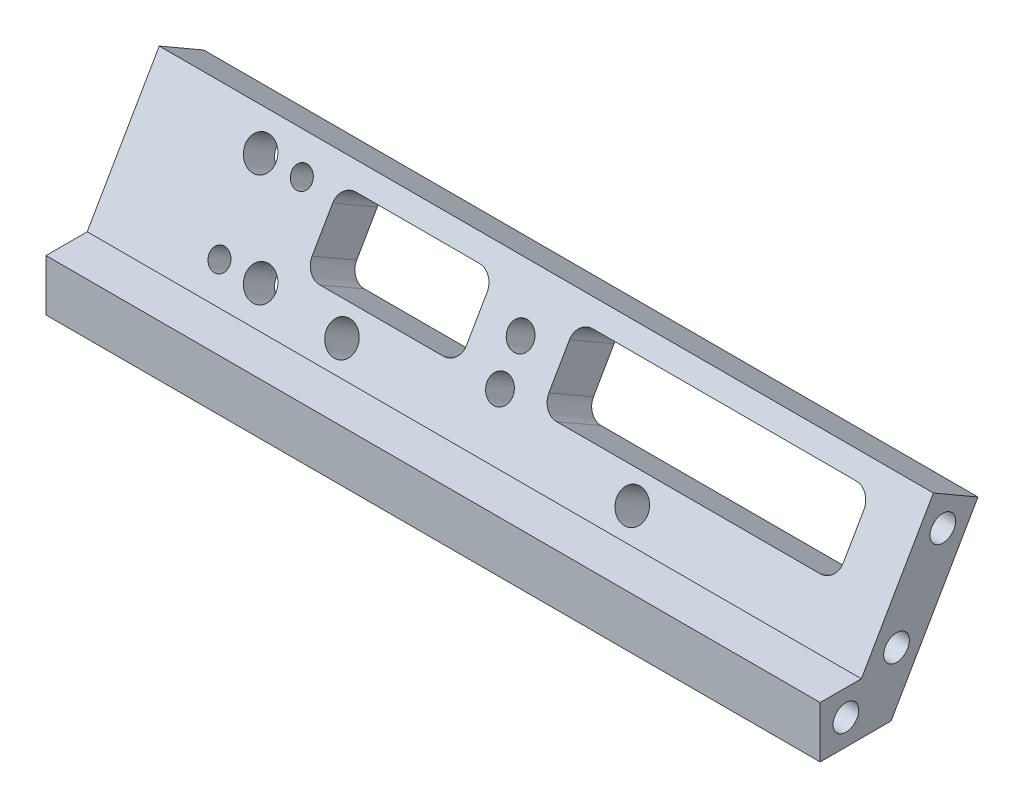
SolidWorks part; units mm, degrees
ref_plane "Front Plane" through (0, 0, 0) normal (0, 0, 1) x (1, 0, 0)
ref_plane "Top Plane" through (0, 0, 0) normal (0, 1, 0) x (1, 0, 0)
ref_plane "Right Plane" through (0, 0, 0) normal (1, 0, 0) x (0, 0, -1)
sketch "Sketch1" plane through (0, 0, 0) normal (1, 0, 0) x (0, 0, -1)
  line L0 (0, 0) -> (6.8868, 0)
  line L1 (6.8868, 0) -> (15.3301, 14.6244)
  line L2 (15.3301, 14.6244) -> (11, 17.1244)
  line L3 (11, 17.1244) -> (4, 5)
  line L4 (4, 5) -> (0, 5)
  line L5 (0, 5) -> (0, 0)
  dimension "D1" = 5
  dimension "D2" = 14
  dimension "D3" = 120
  dimension "D4" = 4
extrude "Boss-Extrude1" add sketch "Sketch1" along normal blind 75.2
hole_wizard "Tap Drill for M3x0.5 Tap1" positions "Sketch3" profile "Sketch2" hole size "M3x0.5" standard "ANSI Metric"
sketch "Sketch3" plane through (75.2, 0, 0) normal (1, 0, 0) x (0, 0, -1)
  line L0 (0, 5) -> (0, 0) construction
  line L1 (6.8868, 0) -> (15.3301, 14.6244) construction
  line L2 (15.3301, 14.6244) -> (11, 17.1244) construction
  line L3 (0, 0) -> (6.8868, 0) construction
  line L4 (11.9151, 13.7093) -> (7.4151, 5.9151) construction
  point P0 (2.5, 2.5)
  point P2 (7.4151, 5.9151)
  point P4 (11.9151, 13.7093)
  dimension "D1" = 2.5
  dimension "D2" = 2.5
  dimension "D3" = 2.5
  dimension "D4" = 9
  dimension "D5" = 2.5
sketch "Sketch2" plane through (75.2, 2.5, -2.5) normal (0, 1, 0) x (0, 0, -1)
  line L0 (0, 0) -> (0, 3.7511)
  line L1 (0, 3.7511) -> (1.25, 3)
  line L2 (1.25, 3) -> (1.25, 0)
  line L5 (1.25, 0) -> (0, 0)
  line L10 (0, 3.7511) -> (-1.25, 3) construction
  line L11 (0, -6.35) -> (0, 107.95) construction
  dimension "Hole Dia." = 2.5
  dimension "Hole Depth" = 3
  dimension "Drill Angle" = 118
hole_wizard "Tap Drill for M3x0.5 Tap2" positions "Sketch5" profile "Sketch4" hole size "M3x0.5" standard "ANSI Metric"
sketch "Sketch5" plane through (0, 0, 0) normal (-1, 0, 0) x (0, 0, 1)
  line L0 (-11.9151, 13.7093) -> (-7.4151, 5.9151) construction
  line L2 (-11, 17.1244) -> (-4, 5) construction
  line L3 (-15.3301, 14.6244) -> (-11, 17.1244) construction
  line L4 (0, 5) -> (0, 0) construction
  line L5 (0, 0) -> (-6.8868, 0) construction
  point P0 (-2.5, 2.5)
  point P2 (-7.4151, 5.9151)
  point P4 (-11.9151, 13.7093)
  dimension "D1" = 2.5
  dimension "D2" = 2.5
  dimension "D3" = 9
  dimension "D4" = 2.5
  dimension "D5" = 2.5
sketch "Sketch4" plane through (0, 2.5, -2.5) normal (0, 1, 0) x (0, 0, 1)
  line L0 (0, 0) -> (0, 3.7511)
  line L1 (0, 3.7511) -> (1.25, 3)
  line L2 (1.25, 3) -> (1.25, 0)
  line L5 (1.25, 0) -> (0, 0)
  line L10 (0, 3.7511) -> (-1.25, 3) construction
  line L11 (0, -6.35) -> (0, 107.95) construction
  dimension "Hole Dia." = 2.5
  dimension "Hole Depth" = 3
  dimension "Drill Angle" = 118
sketch "Sketch6" plane through (0, -0.4821, -0.8349) normal (0, 0.5, 0.866) x (1, 0, 0)
  line L0 (75.2, 20.3301) -> (0, 20.3301) construction
  line L1 (70.2, 18.3301) -> (41.6, 18.3301)
  line L2 (70.2, 18.3301) -> (70.2, 11.3301)
  line L3 (70.2, 11.3301) -> (41.6, 11.3301)
  line L4 (41.6, 18.3301) -> (41.6, 11.3301)
  line L5 (18.6, 18.3301) -> (33.6, 18.3301)
  line L6 (18.6, 18.3301) -> (18.6, 11.3301)
  line L7 (18.6, 11.3301) -> (33.6, 11.3301)
  line L8 (33.6, 18.3301) -> (33.6, 11.3301)
  line L9 (0, 20.3301) -> (0, 6.3301) construction
  line L10 (75.2, 20.3301) -> (75.2, 6.3301) construction
  line L11 (15.35, 17.3301) -> (11.35, 17.3301) construction
  line L12 (15.35, 17.3301) -> (15.35, 9.3301) construction
  line L13 (15.35, 9.3301) -> (11.35, 9.3301) construction
  line L14 (11.35, 17.3301) -> (11.35, 9.3301) construction
  circle A0 centre (23.5, 8.8301) radius 1.5
  circle A1 centre (51.7, 8.8301) radius 1.5
  circle A2 centre (11.35, 17.3301) radius 1.5
  circle A3 centre (15.35, 17.3301) radius 1
  circle A4 centre (11.35, 9.3301) radius 1
  circle A5 centre (15.35, 9.3301) radius 1.5
  dimension "D7" = 3
  dimension "D8" = 2
  dimension "D1" = 7
  dimension "D2" = 2
  dimension "D3" = 4
  dimension "D4" = 11.35
  dimension "D5" = 8
  dimension "D6" = 5
  dimension "D9" = 3
  dimension "D10" = 11.5
  dimension "D11" = 8
  dimension "D12" = 23.5
  dimension "D13" = 23.5
  dimension "D14" = 15
  dimension "D15" = 28.6
extrude "Cut-Extrude1" cut sketch "Sketch6" against normal up to next
fillet "Fillet1" radius 1.5 8 edges at (18.6, 8.0801, -8.6651) (33.6, 8.0801, -8.6651) (33.6, 14.1423, -12.1651) (18.6, 14.1423, -12.1651) (70.2, 8.0801, -8.6651) (41.6, 8.0801, -8.6651) (41.6, 14.1423, -12.1651) (70.2, 14.1423, -12.1651)
chamfer "Chamfer1" distance 1.5 angle 45 2 edges at (15.35, 3.799, -9.0801) (11.35, 10.7272, -13.0801)
hole_wizard "Tap Drill for M3x0.5 Tap3" positions "Sketch8" profile "Sketch7" hole size "M3x0.5" standard "ANSI Metric" end condition up to next
sketch "Sketch8" plane through (0, -0.4821, -0.8349) normal (0, 0.5, 0.866) x (1, 0, 0)
  line L0 (0, 20.3301) -> (0, 6.3301) construction
  line L1 (75.2, 20.3301) -> (0, 20.3301) construction
  point P0 (37.6, 15.3301)
  point P2 (37.6, 11.3301)
  dimension "D1" = 37.6
  dimension "D2" = 9
  dimension "D3" = 4
sketch "Sketch7" plane through (37.6, 12.7942, -8.5) normal (1, 0, 0) x (0, -0.866, 0.5)
  line L0 (0, 0) -> (0, 5)
  line L1 (0, 5) -> (1.25, 5)
  line L2 (1.25, 5) -> (1.25, 0)
  line L5 (1.25, 0) -> (0, 0)
  line L11 (0, -6.35) -> (0, 107.95) construction
  dimension "Thru Hole Dia." = 2.5
  dimension "Thru Hole Depth" = 5
